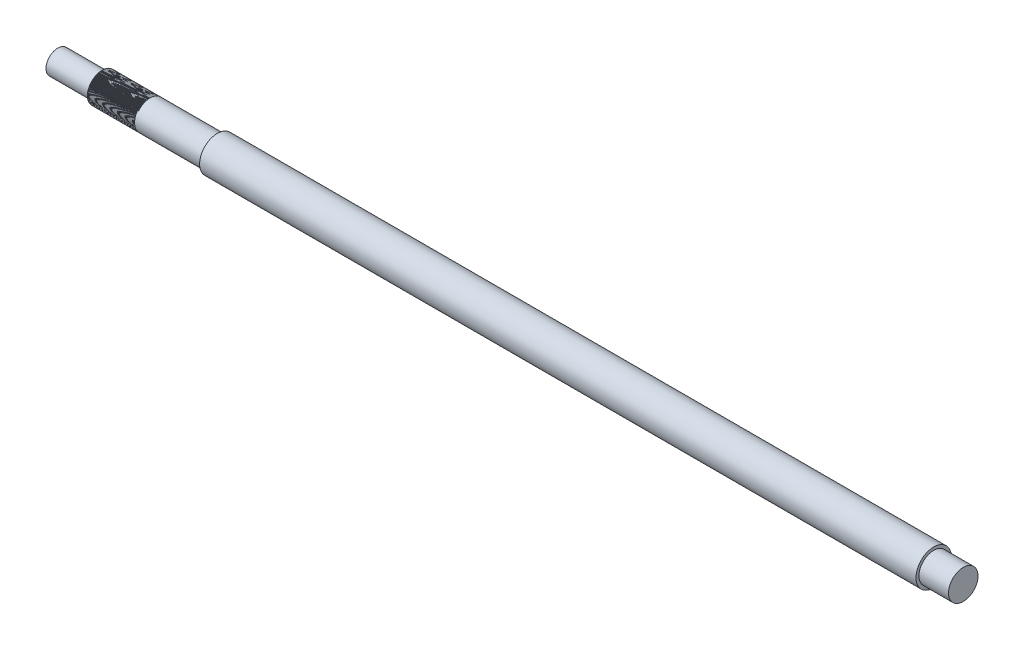
SolidWorks part; units mm, degrees
material "普通碳钢"
ref_plane "前视基准面" through (0, 0, 0) normal (0, 0, 1) x (1, 0, 0)
ref_plane "上视基准面" through (0, 0, 0) normal (0, 1, 0) x (1, 0, 0)
ref_plane "右视基准面" through (0, 0, 0) normal (1, 0, 0) x (0, 0, -1)
other "Configuration Table"
sketch "草图1" plane through (0, 0, 0) normal (0, 0, 1) x (1, 0, 0)
  line L0 (0, 0) -> (30377.1642, 0) construction
  line L1 (0, 0) -> (0, 4)
  line L2 (0, 4) -> (15, 4)
  line L3 (15, 4) -> (15, 5)
  line L4 (15, 5) -> (54, 5)
  line L5 (54, 5) -> (54, 6)
  line L6 (54, 6) -> (296.5, 6)
  line L7 (296.5, 6) -> (296.5, 5)
  line L8 (296.5, 5) -> (306.5, 5)
  line L9 (306.5, 5) -> (306.5, 0)
  line L10 (0, 0) -> (306.5, 0)
  dimension "D1" = 8
  dimension "D2" = 15
  dimension "D3" = 39
  dimension "D4" = 10
  dimension "D5" = 12
  dimension "D6" = 306.5
  dimension "D7" = 10
  dimension "D8" = 10
revolve "旋转1" add sketch "草图1" angle 360 about L0
thread "螺纹线1" pitch 0.3175 method cut profile "螺纹线轮廓1" start angle 0, offset 0, length 16, pitch 0.3175, diameter 10
ref_plane "基准面1" through (15, 0, -5) normal (0, -1, 0) x (0, 0, -1)
sketch "螺纹线轮廓1" plane through (15, 0, -5) normal (0, -1, 0) x (0, 0, -1)
  line L0 (0, 0) -> (0, 0.3175) construction
  line L11 (0, 0) -> (0, 0.2778)
  line L12 (0, 0.2778) -> (-0.1719, 0.1786)
  line L13 (-0.1719, 0.1786) -> (-0.1719, 0.0992)
  line L15 (-0.1719, 0.0992) -> (0, 0)
  line L17 (-0.1719, 0.1389) -> (0, 0.1389) construction
  point P2 (0, 0)
  dimension "Pitch" = 0.3175
  dimension "Profile_Angle" = 60
  dimension "Profile_Land" = 0.0794
  dimension "Profile_Height" = 0.1719
